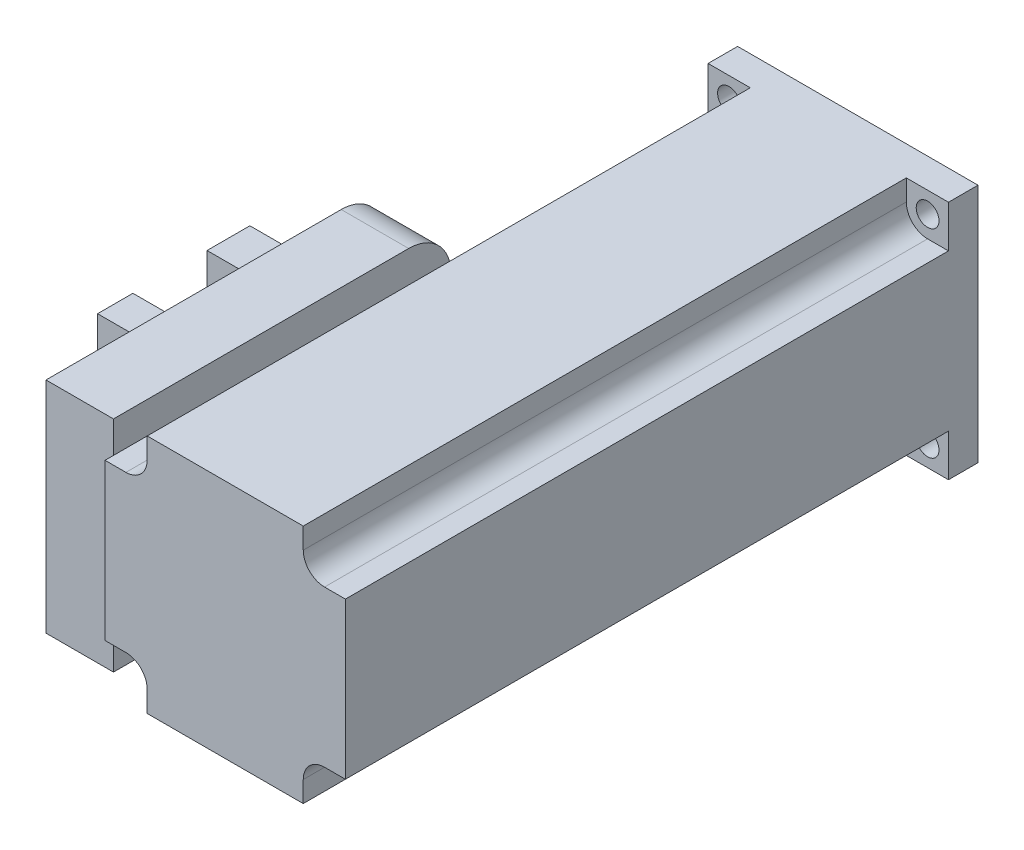
SolidWorks part; units mm, degrees
material "1.5714 (16NiCr4)"
ref_plane "Ebene vorne" through (0, 0, 0) normal (0, 0, 1) x (1, 0, 0)
ref_plane "Ebene oben" through (0, 0, 0) normal (0, 1, 0) x (1, 0, 0)
ref_plane "Ebene rechts" through (0, 0, 0) normal (1, 0, 0) x (0, 0, -1)
sketch "Skizze1" plane through (0, 0, 0) normal (0, 0, 1) x (1, 0, 0)
  line L1 (28.5, -28.5) -> (-28.5, -28.5)
  line L2 (28.5, -28.5) -> (28.5, 28.5)
  line L3 (28.5, 28.5) -> (-28.5, 28.5)
  line L4 (-28.5, -28.5) -> (-28.5, 28.5)
  line L5 (28.5, -28.5) -> (-28.5, 28.5) construction
  line L6 (28.5, 28.5) -> (-28.5, -28.5) construction
  point P0 (0, 0)
  dimension "D1" = 57
  dimension "D2" = 57
extrude "Aufsatz-Linear austragen1" add sketch "Skizze1" along normal blind 150
sketch "Skizze2" plane through (0, 0, 0) normal (0, 0, -1) x (-1, 0, 0)
  circle A0 centre (0, 0) radius 19.05
  dimension "D1" = 38.1
extrude "Aufsatz-Linear austragen2" add sketch "Skizze2" along normal blind 2
sketch "Skizze3" plane through (0, 0, -2) normal (0, 0, -1) x (-1, 0, 0)
  line L0 (-1.9365, -3.5) -> (1.9365, -3.5)
  arc A0 (1.9365, -3.5) -> (-1.9365, -3.5) centre (0, 0) ccw
  dimension "D1" = 8
  dimension "D2" = 3.5
extrude "Aufsatz-Linear austragen3" add sketch "Skizze3" along normal blind 21
sketch "Skizze4" plane through (0, 0, 0) normal (0, 0, -1) x (-1, 0, 0)
  line L0 (0, 35.1407) -> (0, -33.43) construction
  line L1 (-36.7802, 0) -> (37.3504, 0) construction
  circle A0 centre (23.55, 23.55) radius 2.7
  circle A1 centre (-23.55, 23.55) radius 2.7
  circle A2 centre (23.55, -23.55) radius 2.7
  circle A3 centre (-23.55, -23.55) radius 2.7
  dimension "D1" = 47.1
  dimension "D2" = 47.1
  dimension "D3" = 5.4
extrude "Schnitt-Linear austragen1" cut sketch "Skizze4" against normal blind 50
sketch "Skizze5" plane through (0, 0, 0) normal (0, 0, -1) x (-1, 0, 0)
  line L0 (0, 30.1466) -> (0, -32.3466) construction
  line L1 (-31.3497, 0) -> (33.0685, 0) construction
  line L2 (18.5, 23.55) -> (18.5, 28.5)
  line L3 (-28.5, 28.5) -> (28.5, 28.5) construction
  line L4 (18.5, 28.5) -> (28.5, 28.5)
  line L5 (28.5, 28.5) -> (28.5, 18.5)
  line L6 (28.5, 28.5) -> (28.5, -28.5) construction
  line L7 (28.5, 18.5) -> (23.55, 18.5)
  line L8 (-28.5, 28.5) -> (-28.5, 18.5)
  line L9 (-18.5, 28.5) -> (-28.5, 28.5)
  line L10 (-18.5, 23.55) -> (-18.5, 28.5)
  line L11 (-28.5, 18.5) -> (-23.55, 18.5)
  line L12 (28.5, -18.5) -> (23.55, -18.5)
  line L13 (28.5, -28.5) -> (28.5, -18.5)
  line L14 (18.5, -28.5) -> (28.5, -28.5)
  line L15 (18.5, -23.55) -> (18.5, -28.5)
  line L16 (-28.5, -18.5) -> (-23.55, -18.5)
  line L17 (-18.5, -23.55) -> (-18.5, -28.5)
  line L18 (-18.5, -28.5) -> (-28.5, -28.5)
  line L19 (-28.5, -28.5) -> (-28.5, -18.5)
  arc A0 (18.5, 23.55) -> (23.55, 18.5) centre (23.55, 23.55) ccw
  arc A1 (-18.5, 23.55) -> (-23.55, 18.5) centre (-23.55, 23.55) cw
  arc A2 (18.5, -23.55) -> (23.55, -18.5) centre (23.55, -23.55) cw
  arc A3 (-18.5, -23.55) -> (-23.55, -18.5) centre (-23.55, -23.55) ccw
  dimension "D1" = 10
extrude "Schnitt-Linear austragen2" cut sketch "Skizze5" against normal blind 170 from offset 7 offset against normal yes
sketch "Skizze6" plane through (-28.5, 0, 0) normal (-1, 0, 0) x (0, 0, 1)
  line L0 (0, 0) -> (164.4347, 0) construction
  line L1 (150, 18.5) -> (150, -18.5) construction
  line L2 (68, 26) -> (148, 26)
  line L3 (68, 26) -> (68, -26)
  line L4 (68, -26) -> (148, -26)
  line L5 (148, 26) -> (148, -26)
  dimension "D1" = 2
  dimension "D2" = 52
  dimension "D3" = 80
extrude "Aufsatz-Linear austragen4" add sketch "Skizze6" along normal blind 16
fillet "Verrundung1" radius 10 2 edges at (-36.5, 26, 68) (-36.5, -26, 68)
sketch "Skizze7" plane through (-44.5, 0, 0) normal (-1, 0, 0) x (0, 0, 1)
  line L1 (83.6547, 17.4943) -> (93.8127, 17.4943)
  line L2 (83.6547, 17.4943) -> (83.6547, -17.8168)
  line L3 (83.6547, -17.8168) -> (93.8127, -17.8168)
  line L4 (93.8127, 17.4943) -> (93.8127, -17.8168)
  line L5 (111.3876, 17.4943) -> (119.7719, 17.4943)
  line L6 (111.3876, 17.4943) -> (111.3876, -17.8168)
  line L7 (111.3876, -17.8168) -> (119.7719, -17.8168)
  line L8 (119.7719, 17.4943) -> (119.7719, -17.8168)
extrude "Aufsatz-Linear austragen5" add sketch "Skizze7" along normal blind 16
